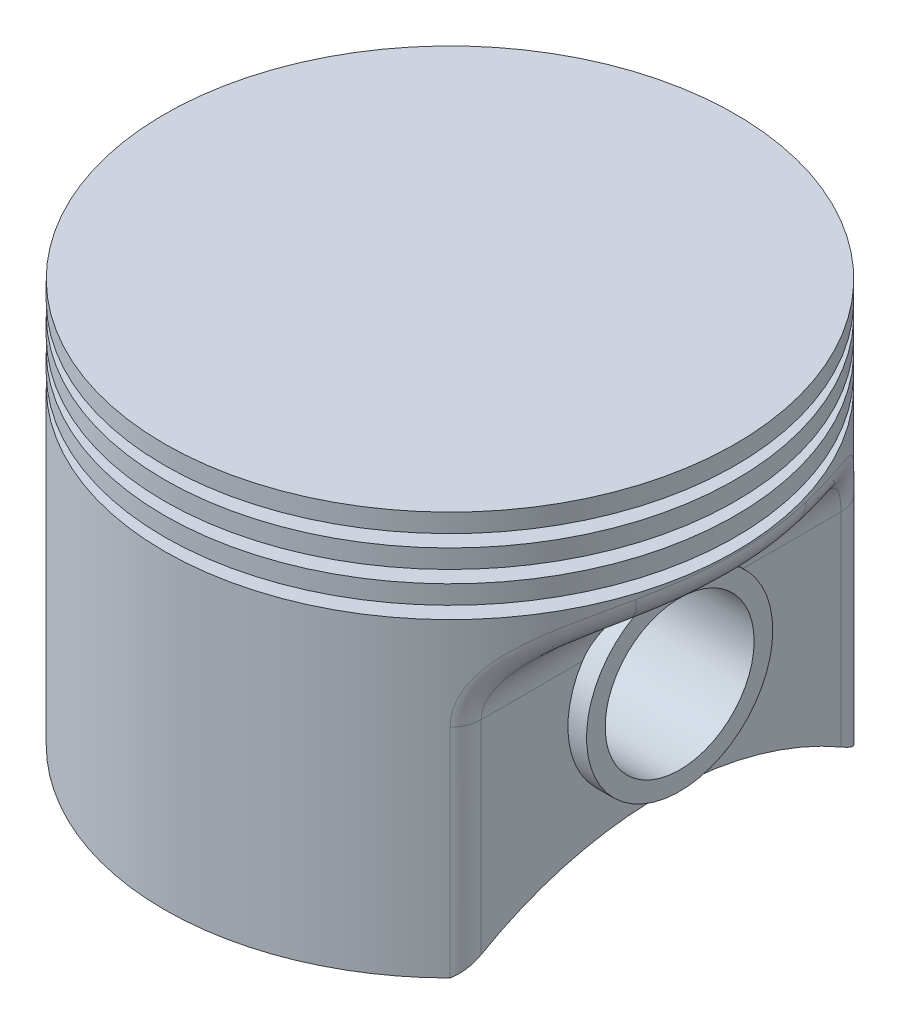
SolidWorks part; units mm, degrees
ref_plane "Front Plane" through (0, 0, 0) normal (0, 0, 1) x (1, 0, 0)
ref_plane "Top Plane" through (0, 0, 0) normal (0, 1, 0) x (1, 0, 0)
ref_plane "Right Plane" through (0, 0, 0) normal (1, 0, 0) x (0, 0, -1)
sketch "Sketch1" plane through (0, 0, 0) normal (0, 1, 0) x (1, 0, 0)
  circle A0 centre (0, 0) radius 46
  dimension "D1" = 92
extrude "Boss-Extrude1" add sketch "Sketch1" against normal blind 65
sketch "Sketch3" plane through (0, 0, 0) normal (0, 0, 1) x (1, 0, 0)
  line L0 (46, 0) -> (46, -3)
  line L1 (46, 0) -> (-46, 0) construction
  line L2 (46, -3) -> (42.5, -3)
  line L3 (42.5, -3) -> (42.5, -5)
  line L4 (42.5, -5) -> (46, -5)
  line L5 (46, -5) -> (46, -8)
  line L6 (46, -8) -> (42.5, -8)
  line L7 (42.5, -8) -> (42.5, -10)
  line L8 (42.5, -10) -> (46, -10)
  line L9 (46, -10) -> (46, -13)
  line L10 (46, -13) -> (42.5, -13)
  line L11 (42.5, -13) -> (42.5, -15)
  line L12 (42.5, -15) -> (46.084, -15)
  line L13 (46.084, -15) -> (55.5676, -15)
  line L14 (55.5676, -15) -> (55.5676, 0)
  line L15 (55.5676, 0) -> (46, 0)
  line L16 (0, 0) -> (0, -68.7974) construction
  dimension "D1" = 3
  dimension "D2" = 2
  dimension "D3" = 3.5
revolve "Cut-Revolve2" cut sketch "Sketch3" angle 360 about L16
sketch "Sketch4" plane through (0, -65, 0) normal (0, -1, 0) x (1, 0, 0)
  line L0 (34, 30.9839) -> (26, 30.9839)
  line L1 (26, 30.9839) -> (26, 17)
  line L2 (26, 17) -> (18, 17)
  line L3 (18, 17) -> (18, -17)
  line L4 (18, -17) -> (26, -17)
  line L5 (26, -17) -> (26, -30.9839)
  line L6 (26, -30.9839) -> (34, -30.9839)
  line L7 (34, -30.9839) -> (34, 30.9839)
  line L8 (0, 0) -> (0, 46) construction
  line L9 (-34, -30.9839) -> (-34, 30.9839)
  line L10 (-26, -30.9839) -> (-34, -30.9839)
  line L11 (-26, -17) -> (-26, -30.9839)
  line L12 (-18, -17) -> (-26, -17)
  line L13 (-18, 17) -> (-18, -17)
  line L14 (-26, 17) -> (-18, 17)
  line L15 (-26, 30.9839) -> (-26, 17)
  line L16 (-34, 30.9839) -> (-26, 30.9839)
  circle A0 centre (0, 0) radius 46 construction
  circle A1 centre (0, 0) radius 46
  arc A2 (-26, -30.9839) -> (26, -30.9839) centre (0, 0) ccw
  arc A3 (26, 30.9839) -> (-26, 30.9839) centre (0, 0) ccw
  point P12 (18, 0)
  circle M19 centre (0, 0) radius 46
  dimension "D1" = 8
  dimension "D2" = 8
  dimension "D3" = 34
  dimension "D4" = 34
extrude "Cut-Extrude1" cut sketch "Sketch4" against normal blind 45 contours L9 M19 | L7 M19 region at (38.8581, -65, 0) region at (-38.8581, -65, 0)
extrude "Cut-Extrude2" cut sketch "Sketch4<3>" against normal blind 45 contours L1 A3 L15 L14 L13 L12 L11 A2 L5 L4 L3 L2 region at (0, -65, 0)
sketch "Sketch4<3>" plane through (0, -65, 0) normal (0, -1, 0) x (1, 0, 0) same geometry as "Sketch4"
sketch "Sketch9" plane through (34, 0, 0) normal (1, 0, 0) x (0, 0, -1)
  line L0 (30.9839, -65) -> (-30.9839, -65) construction
  circle A0 centre (0, -38) radius 12
  circle A1 centre (0, -38) radius 15
  dimension "D2" = 30
  dimension "D3" = 24
  dimension "D1" = 27
extrude "Cut-Extrude7" cut sketch "Sketch9" against normal blind 68 contours A0 region at (34, -38, 0)
extrude "Boss-Extrude3" add sketch "Sketch9<3>" along normal blind 3
sketch "Sketch9<3>" plane through (34, 0, 0) normal (1, 0, 0) x (0, 0, -1) same geometry as "Sketch9"
mirror "Mirror1" about plane through (0, 0, 0) normal (1, 0, 0) of "Boss-Extrude3"
fillet "Fillet1" radius 10 2 edges at (-34, -20, 0) (34, -20, 0)
fillet "Fillet3" radius 5 5 edges at (-34, -47.5, -30.9839) (-34, -47.5, 30.9839) (-35.9205, -24.1075, 28.7353) (-46, -20, 0) (-36.7298, -23.1338, -27.6934)
fillet "Fillet4" radius 5 5 edges at (34, -47.5, 30.9839) (34, -47.5, -30.9839) (35.9205, -24.1075, -28.7353) (46, -20, 0) (36.7298, -23.1338, 27.6934)
sketch "Sketch12" plane through (0, 0, 0) normal (1, 0, 0) x (0, 0, -1)
  line L0 (-32.5172, -65) -> (32.5172, -65)
  line L1 (32.5172, -30) -> (32.5172, -65) construction
  arc A0 (-32.5172, -65) -> (32.5172, -65) centre (0, -113.0274) cw
extrude "Cut-Extrude9" cut sketch "Sketch12" along direction (1, 0, 0) on the side against the normal mid plane 110
